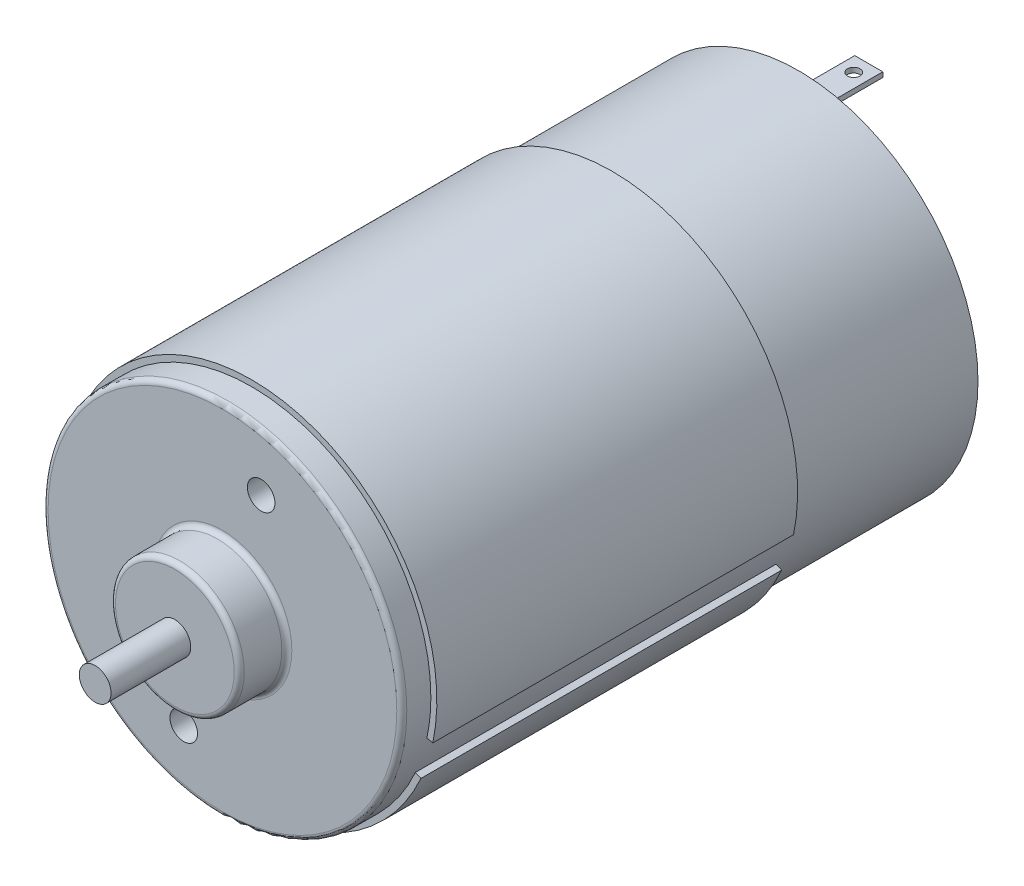
SolidWorks part; units mm, degrees
ref_plane "Front Plane" through (0, 0, 0) normal (0, 0, 1) x (1, 0, 0)
ref_plane "Top Plane" through (0, 0, 0) normal (0, 1, 0) x (1, 0, 0)
ref_plane "Right Plane" through (0, 0, 0) normal (1, 0, 0) x (0, 0, -1)
sketch "Sketch1" plane through (0, 0, 0) normal (0, 0, 1) x (1, 0, 0)
  circle A0 centre (0, 0) radius 17.9
  circle A1 centre (0, 0) radius 5.3
  circle A2 centre (0, 0) radius 1.5875
  dimension "D1" = 35.8
  dimension "D2" = 10.6
  dimension "D3" = 3.175
extrude "Boss-Extrude1" add sketch "Sketch1" along normal blind 57.5 contours A1 A2 | A0 A1 | A2 region at (-17.3937, 0, 0) region at (-5.1501, 0, 0)
extrude "Boss-Extrude2" add sketch "Sketch1<3>" against normal blind 2.8 contours A1 A2 region at (-5.1501, 0, 0)
sketch "Sketch1<3>" plane through (0, 0, 0) normal (0, 0, 1) x (1, 0, 0) same geometry as "Sketch1"
extrude "Boss-Extrude4" add sketch "Sketch1<5>" against normal blind 2 and the other way through all from surface contours A2 region at (0, 0, 0) starting at face at (1.5875, 0, -2.8)
sketch "Sketch1<5>" plane through (0, 0, 0) normal (0, 0, 1) x (1, 0, 0) same geometry as "Sketch1"
extrude "Boss-Extrude5" add sketch "Sketch1<6>" along normal blind 75 from surface contours A2 region at (0, 0, 0) starting at face at (1.5875, 0, -4.8)
sketch "Sketch1<6>" plane through (0, 0, 0) normal (0, 0, 1) x (1, 0, 0) same geometry as "Sketch1"
sketch "Sketch2" plane through (0, 0, 57.5) normal (0, 0, 1) x (1, 0, 0)
  line L0 (0, 19.0096) -> (0, -19.742) construction
  line L1 (-20.7408, 0) -> (23.7703, 0) construction
  line L2 (3.8627, 11.8882) -> (-3.8627, -11.8882) construction
  circle A0 centre (3.8627, 11.8882) radius 1.375
  circle A1 centre (-3.8627, -11.8882) radius 1.375
  circle A2 centre (0, 0) radius 6.425
  point P11 (0, 0)
  dimension "D1" = 2.75
  dimension "D2" = 25
  dimension "D4" = 12.85
  dimension "D3" = 18
extrude "Cut-Extrude1" cut sketch "Sketch2" against normal blind 3 contours A0 | A1 region at (3.8627, 11.8882, 57.5) region at (-3.8627, -11.8882, 57.5)
sketch "Sketch3" plane through (0, 0, 0) normal (0, 0, -1) x (-1, 0, 0)
  line L0 (0, 19.1428) -> (0, -20.0749) construction
  line L1 (-23.7703, 0) -> (22.8048, 0) construction
  line L2 (1.4, -15) -> (1.4, -14.5)
  line L3 (-1.4, 15) -> (1.4, 15)
  line L4 (-1.4, 15) -> (-1.4, 14.5)
  line L5 (-1.4, 14.5) -> (1.4, 14.5)
  line L6 (1.4, 15) -> (1.4, 14.5)
  line L7 (-1.4, -14.5) -> (1.4, -14.5)
  line L8 (-1.4, -15) -> (-1.4, -14.5)
  line L9 (-1.4, -15) -> (1.4, -15)
  point P9 (0, 15)
  dimension "D1" = 2.8
  dimension "D2" = 0.5
  dimension "D3" = 29
extrude "Boss-Extrude6" add sketch "Sketch3" along normal blind 7
sketch "Sketch4" plane through (0, 15, 0) normal (0, 1, 0) x (1, 0, 0)
  line L0 (-1.4, 7) -> (1.4, 7) construction
  circle A0 centre (0, 5.5) radius 0.625
  dimension "D2" = 1.25
  dimension "D1" = 1.5
extrude "Cut-Extrude2" cut sketch "Sketch4" against normal through all
extrude "Boss-Extrude7" add sketch "Sketch2<3>" along normal blind 4.75 contours A2 region at (0, 0, 57.5)
sketch "Sketch2<3>" plane through (0, 0, 57.5) normal (0, 0, 1) x (1, 0, 0) same geometry as "Sketch2"
sketch "Sketch5" plane through (0, 0, 57.5) normal (0, 0, 1) x (1, 0, 0)
  line L0 (18.0939, -3.855) -> (17.5071, -3.73)
  line L1 (16.9042, -7.5166) -> (16.3559, -7.2728)
  line L2 (18.0939, -3.855) -> (16.9042, -7.5166) construction
  line L3 (17.499, -5.6858) -> (-24.6547, 8.0108) construction
  line L4 (18.5, 0) -> (-18.5, 0) construction
  circle A0 centre (0, 0) radius 17.9
  arc A1 (18.0939, -3.855) -> (16.9042, -7.5166) centre (0, 0) ccw
  circle A2 centre (0, 0) radius 17.9 construction
  circle M9 centre (0, 0) radius 17.9
  dimension "D1" = 37
  dimension "D2" = 18
  dimension "D3" = 3.85
extrude "Boss-Extrude8" add sketch "Sketch5" against normal blind 36 from offset 2.9 contours L0 A1 L1 M9 region at (17.9095, -3.2807, 57.5) offset against normal yes
fillet "Fillet1" radius 0.5 4 edges at (17.9, 0, 57.5) (5.3, 0, -2.8) (6.425, 0, 62.25) (6.425, 0, 57.5)
equation "\"3.90.00mm\"=0"
